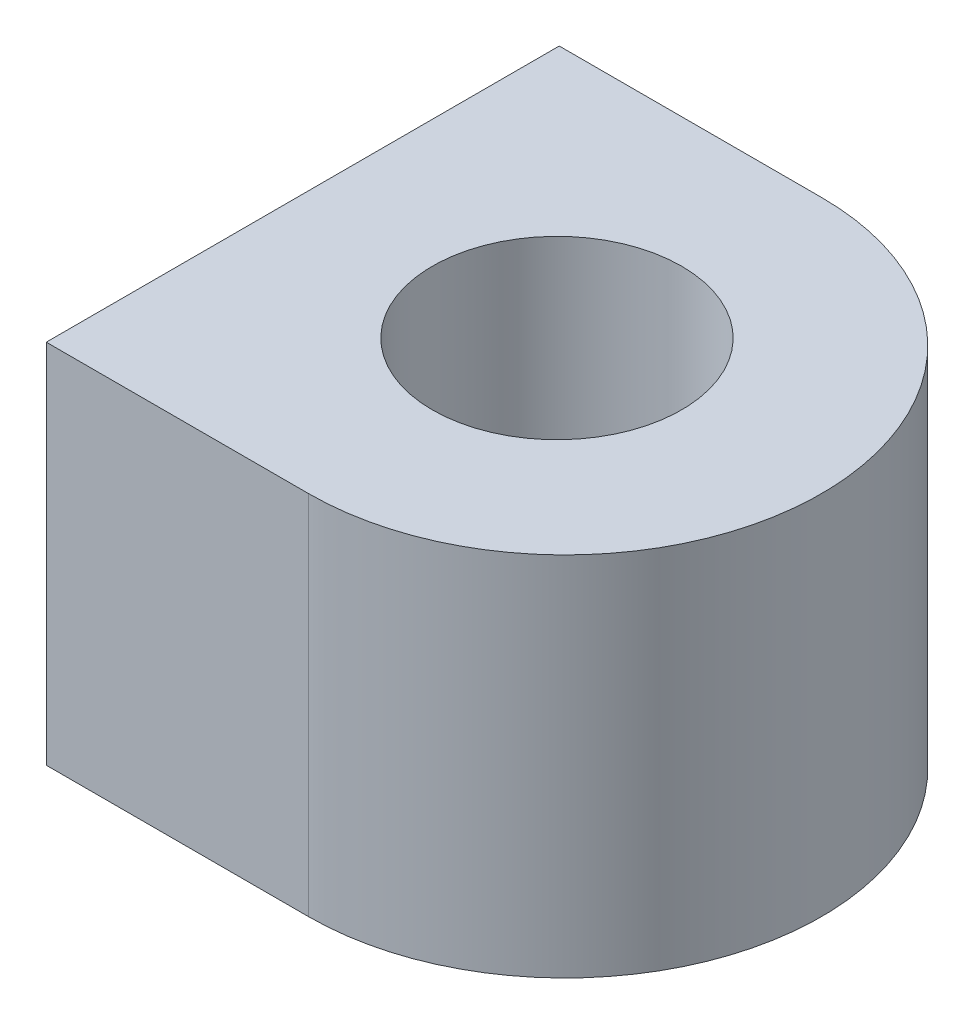
SolidWorks part; units mm, degrees
ref_plane "Front Plane" through (0, 0, 0) normal (0, 0, 1) x (1, 0, 0)
ref_plane "Top Plane" through (0, 0, 0) normal (0, 1, 0) x (1, 0, 0)
ref_plane "Right Plane" through (0, 0, 0) normal (1, 0, 0) x (0, 0, -1)
sketch "Sketch1" plane through (0, 0, 0) normal (0, 1, 0) x (1, 0, 0)
  line L0 (-3.4358, -0.0334) -> (-3.4358, 3.4666)
  line L1 (-3.4358, -0.0334) -> (-3.4358, -3.5334)
  line L5 (-3.4358, -3.5334) -> (0.1437, -3.5334)
  line L6 (-3.4358, 3.4666) -> (0.1437, 3.4666)
  circle A2 centre (0, 0) radius 1.7
  arc A4 (0.1437, 3.4666) -> (0.1437, -3.5334) centre (0.1437, -0.0334) cw
  dimension "D1" = 3.4
  dimension "D3" = 3.4358
  dimension "D2" = 3.5
extrude "Boss-Extrude2" add sketch "Sketch1" along normal blind 5
